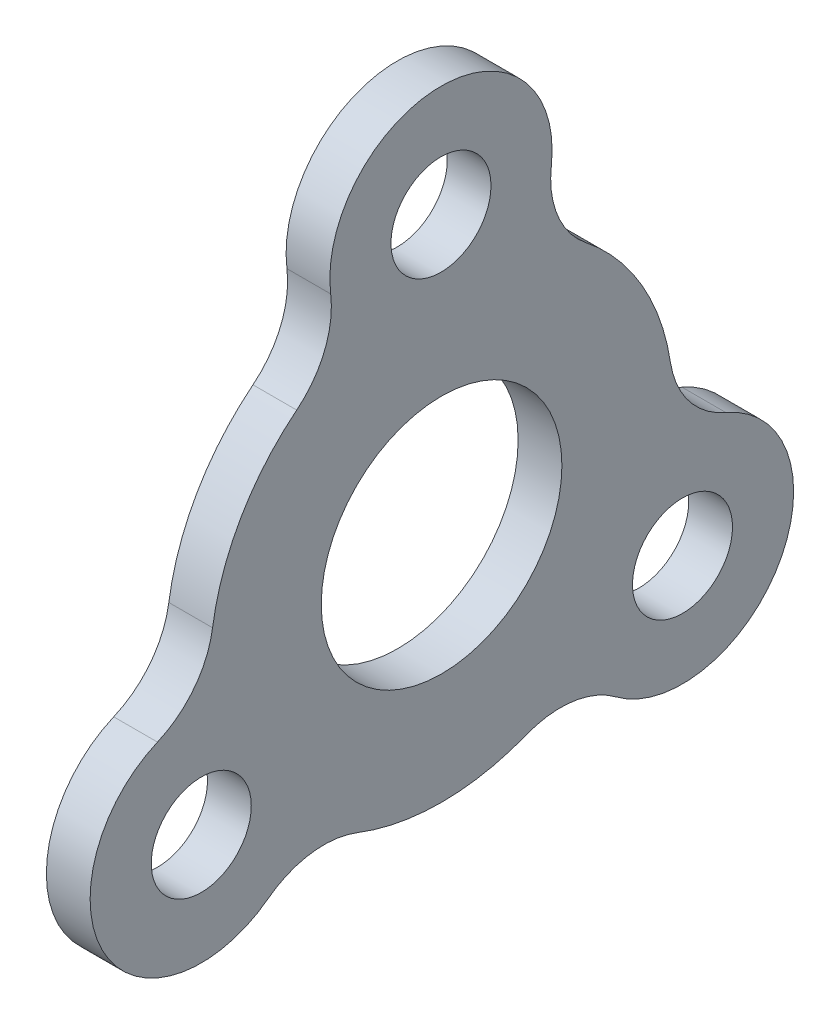
SolidWorks part; units mm, degrees
material "AR500"
ref_plane "Front Plane" through (0, 0, 0) normal (0, 0, 1) x (1, 0, 0)
ref_plane "Top Plane" through (0, 0, 0) normal (0, 1, 0) x (1, 0, 0)
ref_plane "Right Plane" through (0, 0, 0) normal (1, 0, 0) x (0, 0, -1)
sketch "Sketch1" plane through (0, 0, 0) normal (1, 0, 0) x (0, 0, -1)
  line L1 (-0.0412, 19.05) -> (-16.4771, -9.5607) construction
  line L2 (-16.4771, -9.5607) -> (16.5183, -9.4893) construction
  line L3 (16.5183, -9.4893) -> (-0.0412, 19.05) construction
  circle A0 centre (0, 0) radius 8.25
  arc A1 (-9.9327, 12.3837) -> (-15.7013, 2.3422) centre (0, 0) ccw
  circle A2 centre (-0.0412, 19.05) radius 3.429
  circle A3 centre (-16.4771, -9.5607) radius 3.429
  circle A4 centre (16.5183, -9.4893) radius 3.429
  arc A6 (-15.7013, 2.3422) -> (-19.4797, -2.5571) centre (-21.9818, 3.2791) cw
  arc A7 (-19.4797, -2.5571) -> (-11.8868, -15.6429) centre (-16.4771, -9.5607) ccw
  arc A8 (-11.8868, -15.6429) -> (-5.7583, -14.7939) centre (-8.0616, -20.7114) cw
  circle A9 centre (0, 0) radius 19.05 construction
  arc A10 (9.8791, 12.4266) -> (7.5253, 18.1485) centre (13.8307, 17.3972) cw
  arc A11 (7.5253, 18.1485) -> (-7.6037, 18.1157) centre (-0.0412, 19.05) ccw
  arc A12 (-7.6037, 18.1157) -> (-9.9327, 12.3837) centre (-13.9058, 17.3372) cw
  arc A13 (5.8222, -14.7688) -> (11.9544, -15.5913) centre (8.1511, -20.6763) cw
  arc A14 (11.9544, -15.5913) -> (19.4905, -2.4729) centre (16.5183, -9.4893) ccw
  arc A15 (19.4905, -2.4729) -> (15.691, 2.4101) centre (21.9674, 3.3742) cw
  arc A17 (15.691, 2.4101) -> (9.8791, 12.4266) centre (0, 0) ccw
  arc A19 (-5.7583, -14.7939) -> (5.8222, -14.7688) centre (0, 0) ccw
  circle A20 centre (-0.0412, 19.05) radius 2.5527 construction
  point P35 (0, 0)
  dimension "D3" = 16.5
  dimension "D4" = 6.858
  dimension "D5" = 7.62
  dimension "D6" = 6.35
  dimension "D7" = 15.875
  dimension "D2" = 3
extrude "Boss-Extrude1" add sketch "Sketch1" along normal blind 3
equation "\"D3@Sketch1\"=16.5mm"
